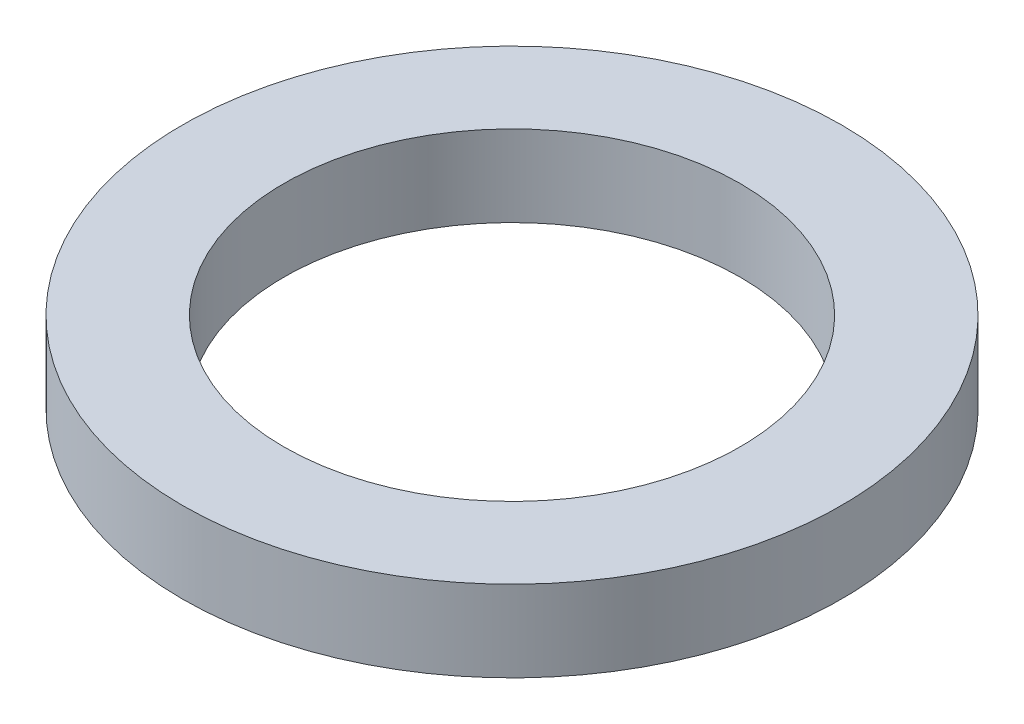
SolidWorks part; units mm, degrees
ref_plane "Front Plane" through (0, 0, 0) normal (0, 0, 1) x (1, 0, 0)
ref_plane "Top Plane" through (0, 0, 0) normal (0, 1, 0) x (1, 0, 0)
ref_plane "Right Plane" through (0, 0, 0) normal (1, 0, 0) x (0, 0, -1)
sketch "Sketch1" plane through (0, 0, 0) normal (0, 1, 0) x (1, 0, 0)
  circle A0 centre (0, 0) radius 32.5
  dimension "FLANGE_OD" = 65
extrude "Boss-Extrude1" add sketch "Sketch1" along normal blind 8
sketch "Sketch2" plane through (0, 0, 0) normal (0, 1, 0) x (1, 0, 0)
  circle A0 centre (0, 0) radius 22.5
  dimension "BORE_D" = 45
extrude "Cut-Extrude1" cut sketch "Sketch2" along normal through all
sketch "Sketch3" plane through (0, 8, 0) normal (0, 1, 0) x (1, 0, 0)
  circle A0 centre (0, 0) radius 13.203 construction
  circle A1 centre (-13.203, 0) radius 1.769
  dimension "BOLT_D" = 3.538
  dimension "BOLT_PCD" = 26.406
extrude "Cut-Extrude2" cut sketch "Sketch3" against normal blind 5.9913 rebuild error yes
pattern_circular "CirPattern1" count 4 over 360 rebuild error yes
